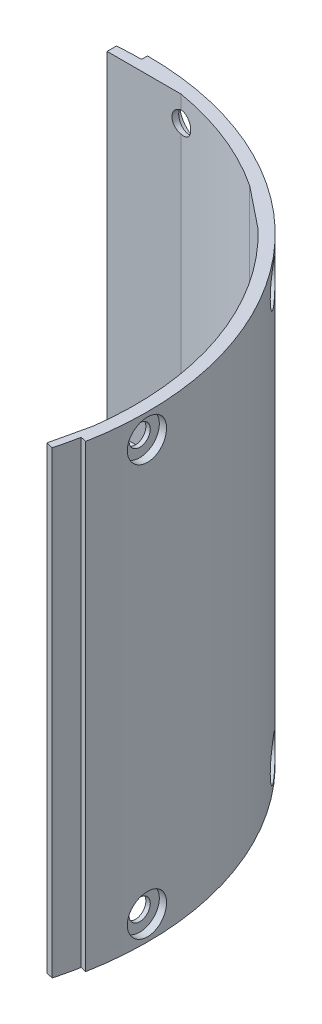
SolidWorks part; units mm, degrees
ref_plane "Спереди" through (0, 0, 0) normal (0, 0, 1) x (1, 0, 0)
ref_plane "Сверху" through (0, 0, 0) normal (0, 1, 0) x (1, 0, 0)
ref_plane "Справа" through (0, 0, 0) normal (1, 0, 0) x (0, 0, -1)
sketch "Эскиз2" plane through (0, 0, 0) normal (0, 1, 0) x (1, 0, 0)
  line L0 (0, -1000) -> (0, 49000) construction
  line L1 (-8.2529, 48.3) -> (8.2529, 48.3) construction
  line L2 (33.9524, 35.3303) -> (27.0476, 40.8587) construction
  line L3 (48.5627, -6.5315) -> (46.5973, -15.1557) construction
  line L4 (-3.9968, 48.3) -> (8.2529, 48.3)
  line L5 (33.9524, 35.3303) -> (27.0476, 40.8587)
  line L6 (48.5627, -6.5315) -> (46.5973, -15.1557) construction
  line L7 (-3.9968, 48.3) -> (-3.9968, 49.84)
  line L10 (-8.2529, 48.3) -> (-3.9968, 48.3) construction
  line L11 (0, 50) -> (0, 51)
  line L12 (0, 0) -> (47.58, -10.8436) construction
  line L16 (47.58, -10.8436) -> (49.725, -11.3324) construction
  line L17 (47.1356, -12.7936) -> (48.5627, -6.5315)
  line L19 (47.1356, -12.7936) -> (48.2666, -13.0514)
  line L20 (50.1312, -9.3737) -> (49.1554, -9.1514)
  circle A0 centre (0, 0) radius 51 construction
  arc A1 (50.1312, -9.3737) -> (0, 51) centre (0, 0) ccw
  circle A2 centre (0, 0) radius 51 construction
  arc A3 (48.5627, -6.5315) -> (33.9524, 35.3303) centre (0, 0) ccw construction
  arc A4 (0, 51) -> (0, -51) centre (0, 0) ccw construction
  arc A5 (48.5627, -6.5315) -> (33.9524, 35.3303) centre (0, 0) ccw
  arc A6 (8.2529, 48.3) -> (27.0476, 40.8587) centre (0, 0) cw
  arc A7 (0, -51) -> (49.725, -11.3324) centre (0, 0) ccw construction
  arc A8 (49.725, -11.3324) -> (50.1312, -9.3737) centre (0, 0) ccw construction
  arc A9 (0, 50) -> (-3.9968, 49.84) centre (0, 0) ccw
  arc A10 (49.1554, -9.1514) -> (48.2666, -13.0514) centre (0, 0) cw
  point P21 (0, 0)
  point P24 (0, 0)
  point P25 (0, 0)
  dimension "D1" = 3.9968
  dimension "D2" = 1
  dimension "D3" = 4
extrude "Бобышка-Вытянуть2" add sketch "Эскиз2" along normal up to surface (76 mm away)
ref_plane "Плоскость4" through (12.7171, 0, -36.1271) normal (-0.332, 0, 0.9433) x (0.9433, 0, 0.332)
sketch "Эскиз7" plane through (12.7171, 0, -36.1271) normal (-0.332, 0, 0.9433) x (0.9433, 0, 0.332)
  line L5 (-8.2529, 17) -> (5.2529, 17) construction
  line L6 (-8.2529, 17) -> (5.2529, 17) construction
  line L7 (8.2529, 14) -> (5.2529, 17) construction
  line L8 (8.2529, 14) -> (5.2529, 17)
  line L9 (-8.2529, 0) -> (8.2529, 0) construction
  line L16 (-8.2529, 0) -> (8.2529, 0)
  line L17 (-8.2529, 76) -> (-8.2529, 0) construction
  line L18 (-8.2529, 17) -> (-8.2529, 0) construction
  line L19 (8.7529, 14.2071) -> (8.7529, 0)
  line L20 (8.7529, 14.2071) -> (5.46, 17.5)
  line L21 (8.2529, 14) -> (8.2529, 0) construction
  line L22 (8.2529, 14) -> (8.2529, 0) construction
  line L23 (-8.7529, 17.5) -> (5.46, 17.5)
  line L24 (-8.7529, 17.5) -> (-8.7529, 0)
  line L25 (-8.7529, 0) -> (-8.2529, 0)
  line L26 (8.2529, 0) -> (8.7529, 0)
  dimension "D1" = 0.5
extrude "Вырез-Вытянуть3" cut sketch "Эскиз7" against normal through all contours L16 L26 L19 L20 L23 L24 L25 region at (12.587, 8.6121, -36.1729)
sketch "Эскиз9" plane through (0, 0, -48.3) normal (0, 0, 1) x (1, 0, 0)
  line L4 (8.7529, 0) -> (8.7529, 17.5)
  line L6 (-3.9968, 76) -> (-3.9968, 0) construction
  line L7 (-3.9968, 19.5032) -> (-3.9968, 0)
  line L8 (-3.9968, 76) -> (-3.9968, 19.5032) construction
  line L9 (-3.9968, 19.5032) -> (-6.5, 17) construction
  line L10 (-8.2529, 0) -> (-3.9968, 0) construction
  line L11 (8.7529, 17.5) -> (6.7071, 17.5)
  line L12 (6.7071, 17.5) -> (3.7071, 20.5)
  line L13 (3.7071, 20.5) -> (-3.7071, 20.5)
  line L14 (-8.2529, 0) -> (8.2529, 0)
  line L15 (8.2529, 0) -> (8.2529, 17)
  line L24 (8.2529, 17) -> (6.5, 17)
  line L25 (6.5, 17) -> (3.5, 20)
  line L26 (3.5, 20) -> (-3.5, 20)
  line L28 (-3.7071, 20.5) -> (-3.9968, 20.2104)
  line L29 (-3.5, 20) -> (-6.5, 17)
  line L30 (-6.5, 17) -> (-8.2529, 17)
  line L31 (-8.2529, 17) -> (-8.2529, 0)
  line L32 (-3.9968, 0) -> (8.2529, 0)
  line L33 (8.2529, 0) -> (8.2529, 17) construction
  line L34 (8.2529, 17) -> (6.5, 17) construction
  line L35 (6.5, 17) -> (3.5, 20) construction
  line L36 (3.5, 20) -> (-3.5, 20) construction
  line L37 (-3.5, 20) -> (-3.9968, 19.5032)
  line L38 (-6.5, 17) -> (-8.2529, 17) construction
  line L39 (-8.2529, 17) -> (-8.2529, 0) construction
  line L40 (-3.9968, 19.5032) -> (-3.9968, 20.2104)
  line L41 (-3.9968, 20.2104) -> (-4.3503, 19.8568) construction
  line L42 (-3.7071, 20.5) -> (-4.3503, 19.8568) construction
  line L43 (8.7529, 0) -> (8.2529, 0)
  line M9 (-8.2529, 0) -> (8.2529, 0)
  line M10 (8.2529, 0) -> (8.2529, 17)
  line M11 (8.2529, 17) -> (6.5, 17)
  line M12 (6.5, 17) -> (3.5, 20)
  line M13 (3.5, 20) -> (-3.5, 20)
  line M14 (-3.5, 20) -> (-6.5, 17)
  dimension "D1" = 0
  dimension "D2" = 0.5
extrude "Вырез-Вытянуть4" cut sketch "Эскиз9" against normal through all contours L7 M14 M9 M10 M11 M12 M13 | L43 L4 L11 L12 L13 L28 L40 M14 M13 M12 M11 M10 region at (8.5029, 0.2414, -48.3) region at (1.9493, 9.6325, -48.3)
sketch "Эскиз10" plane through (0, 12, 0) normal (0, 1, 0) x (1, 0, 0)
  line L0 (-3.9968, 48.3) -> (8.2529, 48.3) construction
  line L1 (-3.9968, 48.3) -> (8.2529, 48.3)
  line L2 (23.8222, 42.8194) -> (20.9924, 43.8155) construction
  line L3 (8.2529, 48.3) -> (20.9924, 43.8155) construction
  line L4 (23.8222, 42.8194) -> (20.9924, 43.8155)
  line L5 (8.2529, 48.3) -> (20.9924, 43.8155)
  line L7 (23.4097, 41.9045) -> (20.6603, 42.8723)
  line L8 (8.082, 47.3) -> (20.6603, 42.8723)
  line L9 (-3.9968, 47.3) -> (8.082, 47.3)
  line L10 (-3.9968, 47.3) -> (-3.9968, 48.3)
  line L11 (26.4956, 40.0248) -> (27.0476, 40.8587) construction
  line L12 (26.4956, 40.0248) -> (28.4646, 39.7241)
  line L13 (27.0476, 40.8587) -> (33.9524, 35.3303) construction
  line L14 (28.4646, 39.7241) -> (27.0476, 40.8587) construction
  line L15 (28.4646, 39.7241) -> (27.0476, 40.8587) construction
  line L16 (28.4646, 39.7241) -> (27.0476, 40.8587)
  arc A0 (27.0476, 40.8587) -> (8.2529, 48.3) centre (0, 0) ccw construction
  arc A1 (27.0476, 40.8587) -> (23.8222, 42.8194) centre (0, 0) ccw
  arc A2 (23.8222, 42.8194) -> (8.2529, 48.3) centre (0, 0) ccw construction
  arc A3 (26.4956, 40.0248) -> (23.4097, 41.9045) centre (0, 0) ccw
  dimension "D2" = 30
  dimension "D1" = 1
extrude "Бобышка-Вытянуть7" add sketch "Эскиз10" along normal blind 10
sketch "Эскиз13" plane through (0, 22, 0) normal (0, 1, 0) x (1, 0, 0)
  line L0 (23.8222, 42.8194) -> (8.2529, 48.3) construction
  line L1 (23.8222, 42.8194) -> (8.2529, 48.3)
  arc A0 (27.0476, 40.8587) -> (8.2529, 48.3) centre (0, 0) ccw construction
  arc A1 (27.0476, 40.8587) -> (8.2529, 48.3) centre (0, 0) ccw
  line M2 (23.8222, 42.8194) -> (8.2529, 48.3)
extrude "Бобышка-Вытянуть8" add sketch "Эскиз13" against normal up to surface (4.5 mm away) contours A1 M2 region at (16.1306, 22, -45.824) up to face at (13.0597, 17.5, -47.6707)
sketch "Эскиз14" plane through (0, 17.5, 0) normal (0, -1, 0) x (1, 0, 0)
  line L0 (21.3189, -44.1192) -> (21.1877, -43.7468)
  line L1 (21.1877, -43.7468) -> (8.2529, -48.3) construction
  line L4 (21.9869, -46.0171) -> (21.3189, -44.1192)
  line L5 (23.8222, -42.8194) -> (8.2529, -48.3)
  line L6 (8.2529, -48.3) -> (6.7071, -48.3)
  line L7 (6.7071, -48.3) -> (6.7071, -50.557)
  line L8 (21.9869, -46.0171) -> (21.3189, -44.1192)
  line L9 (23.8222, -42.8194) -> (21.1877, -43.7468)
  line L10 (8.2529, -48.3) -> (6.7071, -48.3) construction
  line L11 (6.7071, -48.3) -> (6.7071, -50.557) construction
  arc A2 (6.7071, -50.557) -> (21.9869, -46.0171) centre (0, 0) ccw
  arc A3 (21.3189, -44.1192) -> (23.8222, -42.8194) centre (0, 0) ccw
  arc A4 (6.7071, -50.557) -> (21.9869, -46.0171) centre (0, 0) ccw construction
  arc A5 (21.3189, -44.1192) -> (23.8222, -42.8194) centre (0, 0) ccw
  dimension "D1" = 0
extrude "Бобышка-Вытянуть9" add sketch "Эскиз14" along normal up to surface contours A5 L9 L0 up to face at (23.2708, 15.6229, -44.011)
chamfer "Фаска1" distance 1 angle 45 4 edges at (2.0426, 22, -47.3) (15.7459, 22, -44.6022) (24.9703, 22, -40.9937) (27.4801, 22, -39.8745)
ref_plane "Плоскость5" through (51, 0, 0) normal (1, 0, 0) x (0, 0, -1)
sketch "Эскиз15" plane through (51, 0, 0) normal (1, 0, 0) x (0, 0, -1)
  line L0 (0, -1000) -> (0, 49000) construction
  circle A0 centre (0, 4) radius 3.25
  dimension "D1" = 6.5
  dimension "D2" = 4
extrude "Вырез-Вытянуть5" cut sketch "Эскиз15" against normal blind 1.3
sketch "Эскиз16" plane through (49.7, 0, 0) normal (1, 0, 0) x (0, 0, -1)
  circle A0 centre (0, 4) radius 3.25 construction
  circle A1 centre (0, 4) radius 3.25 construction
  circle A2 centre (0, 4) radius 1.75
  dimension "D1" = 3.5
extrude "Вырез-Вытянуть6" cut sketch "Эскиз16" against normal through all
pattern_circular "Круговой массив3" count 3 every 20 about axis through (0, 0, 0) along (0, 1, 0) skipping 1 of "Вырез-Вытянуть5", "Вырез-Вытянуть6"
sketch "Эскиз17" plane through (51, 0, 0) normal (1, 0, 0) x (0, 0, -1)
  line L0 (0, -1000) -> (0, 49000) construction
  line L1 (51, 76) -> (-9.3737, 76) construction
  circle A0 centre (0, 72) radius 3.25
  circle A1 centre (0, 4) radius 3.25 construction
  dimension "D1" = 4
extrude "Вырез-Вытянуть7" cut sketch "Эскиз17" against normal blind 1.3
sketch "Эскиз18" plane through (49.7, 0, 0) normal (1, 0, 0) x (0, 0, -1)
  circle A0 centre (0, 72) radius 3.25 construction
  circle A1 centre (0, 72) radius 3.25 construction
  circle A2 centre (0, 72) radius 1.75
  circle A3 centre (0, 4) radius 1.75 construction
extrude "Вырез-Вытянуть8" cut sketch "Эскиз18" against normal through all
pattern_circular "Круговой массив5" count 5 every 20 about axis through (0, 76, 0) along (0, 1, 0) skipping 1, 3 of "Вырез-Вытянуть8", "Вырез-Вытянуть7"
